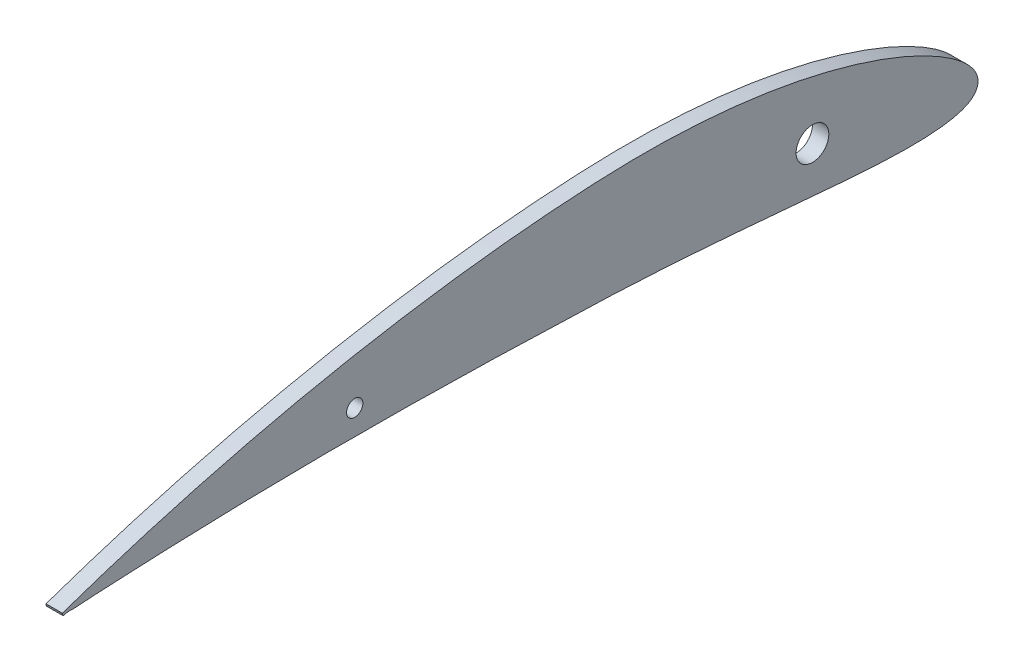
SolidWorks part; units mm, degrees
material "Pine"
ref_plane "Front Plane" through (0, 0, 0) normal (0, 0, 1) x (1, 0, 0)
ref_plane "Top Plane" through (0, 0, 0) normal (0, 1, 0) x (1, 0, 0)
ref_plane "Right Plane" through (0, 0, 0) normal (1, 0, 0) x (0, 0, -1)
curve "Curve1"
  spline degree 3 poles (0, 0.0012, 1.0003) (0, 0.0015, 0.9994) (0, 0.0028, 0.9958) (0, 0.0055, 0.9879) (0, 0.0099, 0.9747) (0, 0.0159, 0.9565) (0, 0.0233, 0.9333) (0, 0.0318, 0.9054) (0, 0.0411, 0.8731) (0, 0.051, 0.8366) (0, 0.0612, 0.7964) (0, 0.0713, 0.7528) (0, 0.0811, 0.7063) (0, 0.0903, 0.6574) (0, 0.0985, 0.6067) (0, 0.1057, 0.5546) (0, 0.1115, 0.5018) (0, 0.1158, 0.4488) (0, 0.1186, 0.3959) (0, 0.1189, 0.3436) (0, 0.1164, 0.2927) (0, 0.1112, 0.2442) (0, 0.1037, 0.1988) (0, 0.0942, 0.157) (0, 0.0831, 0.1194) (0, 0.0711, 0.0865) (0, 0.0584, 0.0585) (0, 0.0457, 0.0357) (0, 0.0334, 0.0184) (0, 0.0218, 0.0064) (0, 0.0108, -0.0005) (0, -0.0003, -0.0011) (0, -0.0092, 0.0055) (0, -0.0148, 0.017) (0, -0.0185, 0.0329) (0, -0.0204, 0.0533) (0, -0.0208, 0.0781) (0, -0.0198, 0.107) (0, -0.0176, 0.1398) (0, -0.0147, 0.176) (0, -0.0111, 0.2153) (0, -0.0074, 0.2574) (0, -0.0037, 0.3019) (0, -0.0005, 0.3484) (0, 0.002, 0.397) (0, 0.0037, 0.4471) (0, 0.0055, 0.4983) (0, 0.0069, 0.5496) (0, 0.0079, 0.6006) (0, 0.0085, 0.6505) (0, 0.0086, 0.699) (0, 0.0083, 0.7455) (0, 0.0076, 0.7894) (0, 0.0065, 0.8302) (0, 0.0053, 0.8675) (0, 0.0039, 0.9007) (0, 0.0027, 0.9296) (0, 0.0013, 0.9539) (0, 0.0006, 0.9727) (0, -0.0011, 0.9872) (0, 0, 0.9944) (0, -0.002, 0.9999) (0, -0.0005, 1) (0, 0, 1) knots 0 0 0 0 0.001372 0.005465 0.012235 0.021602 0.033461 0.047671 0.064081 0.082496 0.102719 0.124527 0.147676 0.171913 0.196978 0.222597 0.248497 0.274385 0.300041 0.32569 0.350525 0.37428 0.396711 0.417577 0.436654 0.453744 0.46868 0.481329 0.491631 0.499616 0.505546 0.510185 0.514824 0.520702 0.528516 0.538466 0.550543 0.564643 0.580638 0.598345 0.617584 0.638174 0.659922 0.682632 0.706121 0.730727 0.7557 0.780732 0.805564 0.829932 0.85357 0.876213 0.89761 0.917519 0.935698 0.951943 0.966047 0.97784 0.987174 0.993932 0.998018 0.999386 1 1 1 1
sketch "Sketch1" plane through (0, 0, 0) normal (1, 0, 0) x (0, 0, -1)
  line L0 (-354.7873, -0.0303) -> (-354.8762, 0.4104)
  line L1 (-354.7873, -0.0303) -> (0.8093, 1.5275) construction
  line L2 (0.8093, 1.5275) -> (0.7921, 5.4415) construction
  spline S1 degree 3 poles (-354.8762, 0.4104) (-354.5599, 0.5194) (-353.2997, 0.9536) (-350.4787, 1.9271) (-345.801, 3.4978) (-336.0241, 6.7216) (-319.6545, 11.7989) (-300.5983, 17.1306) (-282.4229, 21.7243) (-261.1758, 26.6516) (-238.6223, 31.1455) (-208.7748, 36.0048) (-183.9617, 39.0905) (-158.9023, 41.1132) (-140.0967, 42.1114) (-121.5167, 42.2289) (-103.4222, 41.3211) (-86.1884, 39.4787) (-70.0435, 36.8105) (-55.1998, 33.4329) (-41.8434, 29.5109) (-30.1305, 25.2201) (-20.187, 20.7343) (-12.1072, 16.2263) (-5.9269, 11.8553) (-1.6792, 7.7165) (0.7658, 3.7968) (0.9875, -0.1483) (-1.3511, -3.3089) (-5.4508, -5.2881) (-11.0873, -6.5875) (-18.3491, -7.2685) (-27.1638, -7.4049) (-37.4471, -7.0538) (-49.0831, -6.3019) (-61.9524, -5.238) (-75.9299, -3.9839) (-96.4067, -2.1536) (-117.9372, -0.4584) (-140.4848, 0.6745) (-158.2965, 1.2867) (-176.4839, 1.9179) (-200.672, 2.5862) (-224.5411, 2.9791) (-247.8302, 3.0285) (-264.3373, 2.9074) (-279.9331, 2.6564) (-294.438, 2.2829) (-307.6819, 1.8521) (-319.5134, 1.3711) (-329.7674, 0.9129) (-338.3889, 0.4268) (-345.077, 0.1915) (-350.2276, -0.4064) (-352.7802, -0.0354) (-354.7446, -0.7581) (-354.7772, -0.2025) (-354.7873, -0.0303) knots 0 0 0 0 0.001372 0.005465 0.012235 0.021602 0.047671 0.082496 0.102719 0.124527 0.171913 0.196978 0.248497 0.274385 0.300041 0.32569 0.350525 0.37428 0.396711 0.417577 0.436654 0.453744 0.46868 0.481329 0.491631 0.499616 0.505546 0.510185 0.514824 0.520702 0.528516 0.538466 0.550543 0.564643 0.580638 0.598345 0.617584 0.638174 0.682632 0.706121 0.730727 0.7557 0.780732 0.829932 0.85357 0.876213 0.89761 0.917519 0.935698 0.951943 0.966047 0.97784 0.987174 0.993932 0.998018 0.999386 1 1 1 1
  dimension "D1" = 355.6
extrude "Boss-Extrude1" add sketch "Sketch1" along normal blind 3.175 and the other way blind 3.175
sketch "Sketch2" plane through (-3.175, 0, 0) normal (-1, 0, 0) x (0, 0, 1)
  line L0 (0, -3.4925) -> (0, 3.4925) construction
  line L1 (3.4925, 0) -> (-3.4925, 0) construction
  circle A0 centre (63.5, 12.7) radius 6.35
  circle A1 centre (241.3, 12.7) radius 3.175
  dimension "D1" = 12.7
  dimension "D2" = 6.35
  dimension "D3" = 63.5
  dimension "D4" = 12.7
  dimension "D5" = 12.7
  dimension "D6" = 241.3
extrude "Cut-Extrude1" cut sketch "Sketch2" against normal through all both and the other way through all
